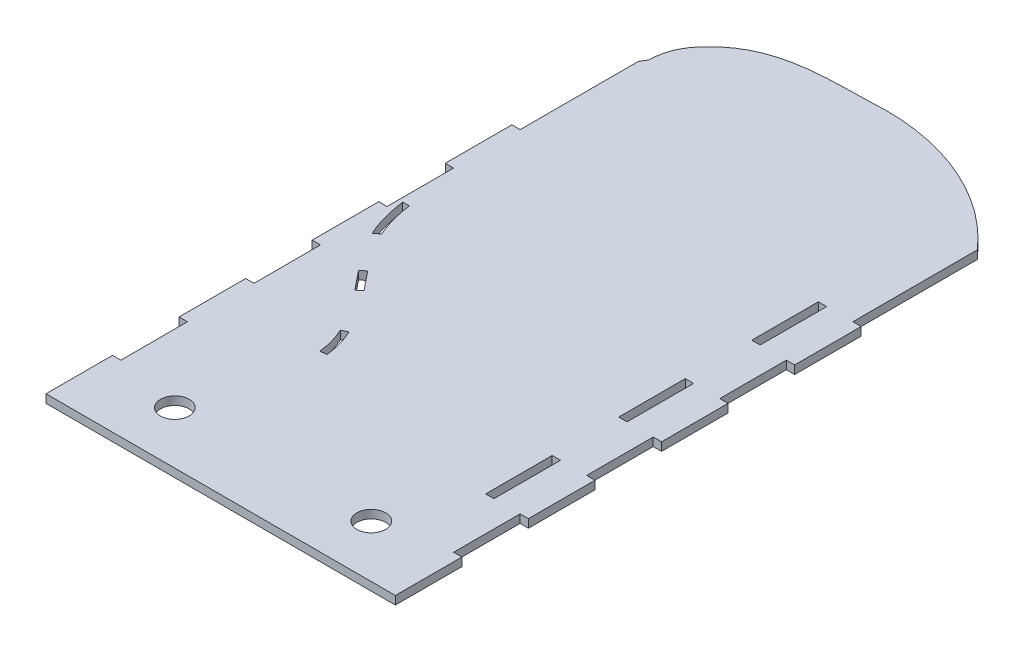
SolidWorks part; units mm, degrees
ref_plane "Front Plane" through (0, 0, 0) normal (0, 0, 1) x (1, 0, 0)
ref_plane "Top Plane" through (0, 0, 0) normal (0, 1, 0) x (1, 0, 0)
ref_plane "Right Plane" through (0, 0, 0) normal (1, 0, 0) x (0, 0, -1)
sketch "Sketch2" plane through (0, 0, 0) normal (0, 1, 0) x (1, 0, 0)
  line L0 (127, 0) -> (127, 40) construction
  line L1 (0, 0) -> (254, 0)
  line L2 (0, 0) -> (0, 508)
  line L3 (0, 508) -> (254, 508)
  line L4 (254, 0) -> (254, 508)
  line L5 (112, 0) -> (112, 40) construction
  line L6 (70.0293, 132.7246) -> (75.0014, 133.2514)
  line L8 (3.0464, 262.9295) -> (8.0974, 262.9295)
  line L9 (12.0177, 230.6311) -> (16.1196, 233.6878)
  line L10 (63.9635, 154.4733) -> (68.5195, 156.533)
  line L11 (31.3299, 200.9155) -> (35.2571, 204.0102)
  line L12 (42.9806, 186.4099) -> (46.8891, 189.5281)
  circle A0 centre (52, 40) radius 11
  circle A1 centre (202, 40) radius 11
  spline S0 degree 3 poles (0, 358) (10.2414, 318.2744) (-10.3205, 225.9555) (70.6512, 174.3118) (75.0014, 133.2514) knots 0 0 0 0 0.517006 1 1 1 1 construction
  spline S1 degree 3 poles (57.0275, 368.1055) (60.011, 340.8516) (38.8621, 298.2828) (61.0822, 235.4033) (84.5865, 206.7018) (104.9746, 198.8412) knots 0 0 0 0 0.426438 0.676001 1 1 1 1 construction
  spline S2 degree 1 poles (-4.8417, 356.7518) (70.0293, 132.7246) knots 0 0 1 1 construction
  spline S3 degree 3 poles (-4.8417, 356.7518) (-4.2453, 354.4384) (-3.2098, 349.8001) (-1.6146, 340.1963) (-0.4104, 327.7832) (0.2492, 312.4005) (0.7261, 291.8409) (1.4026, 275.812) (2.8811, 264.0829) (3.206, 261.7747) (3.5674, 259.4757) (3.9542, 257.1833) (4.5302, 254.1018) (5.5014, 249.6086) (6.6895, 245.0428) (8.2086, 240.135) (9.6429, 236.1559) (11.2633, 232.2426) (12.5555, 229.4544) (14.3601, 225.8497) (18.1885, 218.946) (23.3984, 211.2859) (29.2816, 203.4962) (32.93, 198.8824) (36.8298, 194.0373) (40.7355, 189.2215) (46.6866, 181.7864) (53.9965, 172.1125) (59.9683, 162.643) (63.1245, 156.3309) (64.1438, 154.0765) (64.4933, 153.279) (64.8362, 152.4792) (65.7137, 150.3629) (66.7102, 147.6655) (67.6191, 144.7625) (68.2641, 142.4625) (68.8611, 140.0122) (69.3531, 137.5307) (69.7433, 135.1238) (69.9343, 133.621) (70.0293, 132.7246) knots 0 0 0 0 0.03125 0.0625 0.125 0.1875 0.25 0.371368 0.378402 0.392471 0.399505 0.406539 0.420608 0.4375 0.462351 0.477976 0.5 0.513677 0.529302 0.537114 0.5625 0.625 0.649179 0.680429 0.696054 0.724459 0.755709 0.8125 0.875 0.898852 0.904562 0.907417 0.910272 0.915981 0.9375 0.948072 0.955885 0.96875 0.980913 0.988548 1 1 1 1 only from (0, 317.7537) to (70.0293, 132.7246) construction
  spline S4 degree 1 poles (35.2571, 204.0102) (46.8891, 189.5281) knots 0 0 1 1
  spline S5 degree 1 poles (31.3299, 200.9155) (42.9806, 186.4099) knots 0 0 1 1
  spline S6 degree 3 poles (3.0464, 262.9295) (4.6075, 251.8412) (7.2857, 240.8284) (12.0177, 230.6311) knots 0 0 0 0 1 1 1 1
  spline S7 degree 3 poles (8.0974, 262.9295) (9.5523, 252.911) (11.965, 242.952) (16.1196, 233.6878) knots 0 0 0 0 1 1 1 1
  spline S8 degree 3 poles (68.5195, 156.533) (70.3934, 152.3928) (73.1628, 144.7538) (74.6292, 136.7727) (75.0014, 133.2514) knots 0 0 0 0 0.562151 1 1 1 1
  spline S9 degree 3 poles (63.9635, 154.4733) (65.5406, 150.9864) (68.1883, 143.8779) (69.6381, 136.4314) (70.0293, 132.7246) knots 0 0 0 0 0.506681 1 1 1 1
  point P44 (0, 0)
  point P47 (0, 0)
  dimension "D3" = 22
  dimension "D1" = 508
  dimension "D2" = 254
  dimension "D4" = 40
  dimension "D5" = 15
  dimension "D6" = 60
  dimension "D7" = 150
  dimension "D8" = 5
extrude "Boss-Extrude1" add sketch "Sketch2" along normal blind 6.35
sketch "Sketch3" plane through (0, 6.35, 0) normal (0, 1, 0) x (1, 0, 0)
  line L0 (127, 508) -> (127, 338.6667) construction
  line L1 (254, 508) -> (0, 508) construction
  line L2 (127, 338.6667) -> (127, 169.3333) construction
  line L3 (127, 169.3333) -> (127, 0) construction
  line L4 (0, 0) -> (254, 0) construction
  line L5 (254, 0) -> (254, 508) construction
  line L6 (254, 508) -> (127, 508)
  line L7 (254, 450.6701) -> (254, 508)
  arc A1 (127, 508) -> (254, 450.6701) centre (127, 338.6667) cw
extrude "Cut-Extrude1" cut sketch "Sketch3" against normal up to next
sketch "Sketch5" plane through (0, 6.35, 0) normal (0, 1, 0) x (1, 0, 0)
  line L0 (254, 450.6701) -> (0, 450.6701) construction
  line L1 (0, 508) -> (0, 0) construction
  line L2 (3, 450.6701) -> (0, 445.8071)
  line L3 (0, 508) -> (0, 445.8071)
  line L6 (0, 508) -> (0, 526.7662)
  line L7 (0, 526.7662) -> (127, 526.7662)
  line L8 (127, 508) -> (127, 526.7662)
  circle A0 centre (45, 450.6701) radius 22 construction
  arc A2 (16.9934, 481.9692) -> (3, 450.6701) centre (45, 450.6701) ccw
  circle A3 centre (45, 450.6701) radius 42 construction
  spline S0 degree 3 poles (16.9934, 481.9692) (44.7711, 511.7661) (91.2093, 505.8566) (127, 508) knots 0 0 0 0 1 1 1 1
  dimension "D1" = 44
  dimension "D3" = 45
  dimension "D2" = 20
extrude "Cut-Extrude2" cut sketch "Sketch5" against normal up to next
sketch "Sketch7" plane through (0, 0, 0) normal (0, -1, 0) x (1, 0, 0)
  line L1 (254, 0) -> (260.35, 0)
  line L2 (254, 0) -> (254, -50.8)
  line L3 (254, -50.8) -> (260.35, -50.8)
  line L4 (260.35, 0) -> (260.35, -50.8)
  line L5 (0, 0) -> (-6.35, 0)
  line L6 (0, 0) -> (0, -50.8)
  line L7 (0, -50.8) -> (-6.35, -50.8)
  line L8 (-6.35, 0) -> (-6.35, -50.8)
  dimension "D1" = 6.35
  dimension "D2" = 50.8
  dimension "D3" = 6.35
  dimension "D4" = 50.8
extrude "Boss-Extrude2" add sketch "Sketch7" against normal up to surface (6.35 mm away) up to face at (9.7017, 6.35, -247.9266)
pattern_linear "LPattern1" count 4 spacing 101.6 along (0, 0, -1) of "Boss-Extrude2"
sketch "Sketch8" plane through (0, 6.35, 0) normal (0, 1, 0) x (1, 0, 0)
  line L0 (254, 152.4) -> (254, 203.2) construction
  line L5 (234, 152.4) -> (227.65, 152.4)
  line L7 (234, 152.4) -> (234, 101.6)
  line L9 (234, 101.6) -> (227.65, 101.6)
  line L10 (227.65, 152.4) -> (227.65, 101.6)
  line L11 (254, 101.6) -> (260.35, 101.6) construction
  line L12 (260.35, 101.6) -> (260.35, 152.4) construction
  dimension "D1" = 20
extrude "Cut-Extrude3" cut sketch "Sketch8" against normal up to next
pattern_linear "LPattern2" count 3 spacing 101.6 along (0, 0, -1) of "Cut-Extrude3"
sketch "Slider" plane through (0, 6.35, 6.35) normal (0, 1, 0) x (1, 0, 0)
  line L0 (0, 452.1571) -> (0, 361.95) construction
  line L6 (69.9341, 139.1196) -> (74.9062, 139.6472) construction
  spline S0 degree 3 poles (0, 364.2407) (10.0682, 324.5396) (-10.3334, 232.3175) (70.5497, 180.7071) (74.9062, 139.6472) knots 0 0 0 0 0.516673 1 1 1 1 construction
  spline S1 degree 3 poles (57.0275, 368.1055) (60.011, 340.8516) (38.8621, 298.2828) (61.0822, 235.4033) (84.5865, 206.7018) (104.9746, 198.8412) knots 0 0 0 0 0.426438 0.676001 1 1 1 1 construction
  spline S2 degree 1 poles (-4.8466, 363.0116) (69.9341, 139.1196) knots 0 0 1 1 construction
  spline S3 degree 3 poles (-4.8466, 363.0116) (-4.2595, 360.6968) (-3.2413, 356.0572) (-1.6749, 346.4509) (-0.4966, 334.0377) (0.1461, 318.6588) (0.6231, 297.8055) (1.5286, 276.8267) (4.9993, 256.4703) (8.7041, 244.1769) (12.9114, 234.7192) (17.8624, 225.6809) (25.1267, 215.0112) (34.7565, 202.8262) (44.5247, 190.8853) (53.6801, 178.861) (60.1908, 168.5306) (64.3917, 159.9393) (66.9624, 153.2933) (68.5604, 147.5401) (69.4736, 142.793) (69.8044, 140.3417) (69.9341, 139.1196) knots 0 0 0 0 0.03125 0.0625 0.125 0.1875 0.25 0.375 0.4375 0.5 0.53125 0.5625 0.625 0.6875 0.75 0.8125 0.875 0.90625 0.9375 0.96875 0.984375 1 1 1 1 only from (0, 321.5008) to (69.9341, 139.1196) construction
  point P0 (0, 364.2407)
  point P44 (0, 0)
  point P47 (0, 0)
  dimension "D8" = 5
